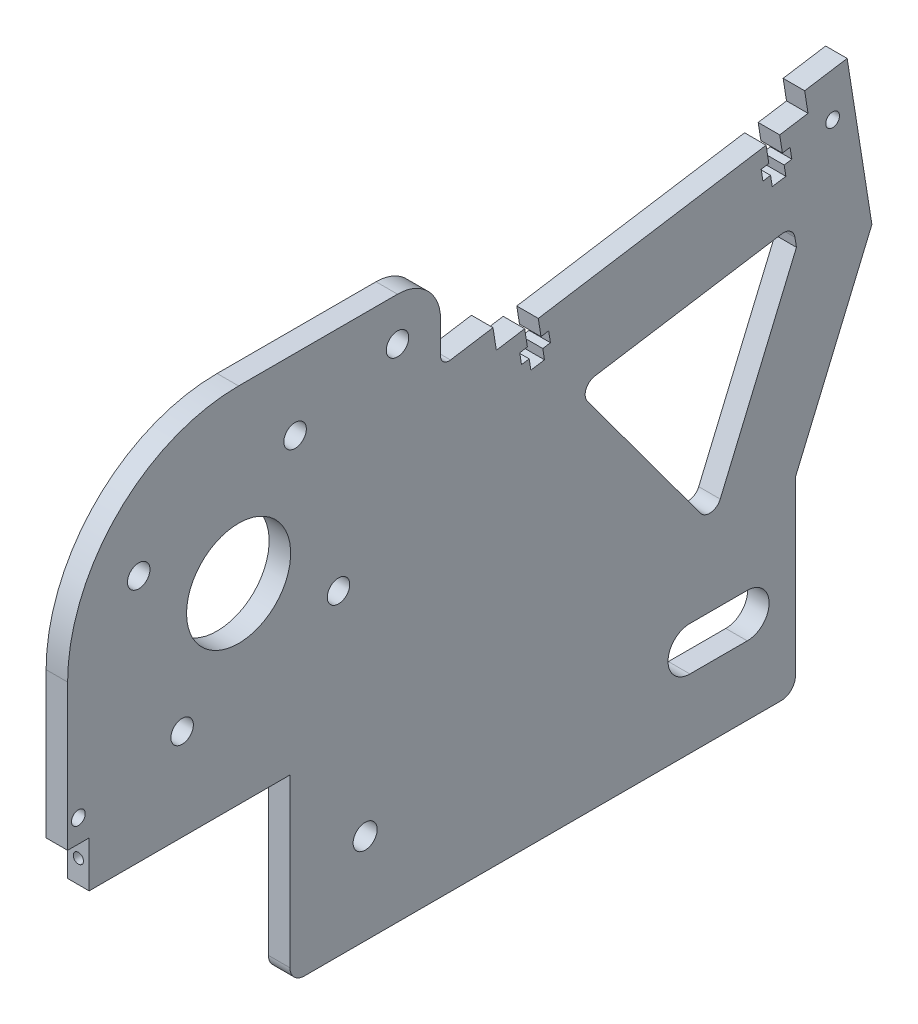
SolidWorks part; units mm, degrees
ref_plane "Front Plane" through (0, 0, 0) normal (0, 0, 1) x (1, 0, 0)
ref_plane "Top Plane" through (0, 0, 0) normal (0, 1, 0) x (1, 0, 0)
ref_plane "Right Plane" through (0, 0, 0) normal (1, 0, 0) x (0, 0, -1)
sketch "Sketch1" plane through (0, 0, 0) normal (1, 0, 0) x (0, 0, -1)
  line L0 (-28.1703, 0) -> (77.3828, 0)
  line L1 (80.5578, 3.175) -> (80.5578, 41.307)
  line L2 (-80.5578, 82.55) -> (-80.5578, 50.292)
  line L3 (4.1952, 101.9194) -> (13.6029, 103.4094)
  line L4 (-75.7953, 50.292) -> (-75.7953, 40.132)
  line L5 (-80.5578, 50.292) -> (-75.7953, 50.292)
  line L6 (69.8898, 20.066) -> (57.1898, 20.066) construction
  line L7 (-75.7953, 40.132) -> (-31.3453, 40.132)
  line L8 (1.9922, 110.875) -> (1.9922, 103.8009)
  line L9 (-42.7078, 120.4) -> (-7.5328, 120.4)
  line L10 (-31.3453, 40.132) -> (-31.3453, 3.175)
  line L11 (-37.9611, 96.6304) -> (82.0608, 56.1697) construction
  line L12 (-52.1443, 71.0721) -> (45.6937, -9.3646) construction
  line L13 (69.8898, 15.2273) -> (57.1898, 15.2273)
  line L14 (69.8898, 24.9047) -> (57.1898, 24.9047)
  line L15 (4.1952, 101.9194) -> (101.0919, 101.9194) construction
  line L16 (13.6029, 103.4094) -> (14.348, 98.7055)
  line L17 (14.348, 98.7055) -> (20.6198, 99.6989)
  line L18 (83.338, 109.6325) -> (82.593, 114.3363)
  line L19 (82.593, 114.3363) -> (92.0007, 115.8264)
  line L20 (92.0007, 115.8264) -> (97.4765, 81.2539)
  line L21 (97.4765, 81.2539) -> (80.5578, 41.307)
  line L22 (20.6198, 99.6989) -> (21.2208, 95.9044)
  line L23 (21.2208, 95.9044) -> (19.5274, 95.6362)
  line L24 (19.5274, 95.6362) -> (19.9198, 93.1589)
  line L25 (19.9198, 93.1589) -> (21.6131, 93.4271)
  line L26 (26.317, 94.1721) -> (25.9246, 96.6495)
  line L27 (25.9246, 96.6495) -> (24.2312, 96.3812)
  line L28 (24.2312, 96.3812) -> (23.6303, 100.1757)
  line L29 (23.6303, 100.1757) -> (74.0557, 108.1623)
  line L30 (77.0662, 108.6391) -> (83.338, 109.6325)
  line L31 (80.4436, 87.3149) -> (80.7745, 85.2255)
  line L38 (21.6131, 93.4271) -> (21.9857, 91.0751)
  line L39 (21.9857, 91.0751) -> (24.9961, 91.5519)
  line L40 (24.9961, 91.5519) -> (24.6236, 93.9039)
  line L41 (24.6236, 93.9039) -> (26.317, 94.1721)
  line L46 (74.0557, 108.1623) -> (74.6567, 104.3679)
  line L47 (77.5375, 89.4263) -> (36.1485, 82.8709)
  line L48 (34.5006, 78.856) -> (59.5216, 44.8808)
  line L49 (63.9057, 45.3965) -> (80.7745, 85.2255)
  line L50 (74.6567, 104.3679) -> (72.9633, 104.0996)
  line L51 (72.9633, 104.0996) -> (73.3557, 101.6223)
  line L52 (73.3557, 101.6223) -> (75.0491, 101.8905)
  line L53 (79.7529, 102.6355) -> (79.3605, 105.1129)
  line L54 (79.3605, 105.1129) -> (77.6672, 104.8447)
  line L55 (77.6672, 104.8447) -> (77.0662, 108.6391)
  line L56 (75.0491, 101.8905) -> (75.4216, 99.5385)
  line L57 (75.4216, 99.5385) -> (78.432, 100.0154)
  line L58 (78.432, 100.0154) -> (78.0595, 102.3673)
  line L59 (78.0595, 102.3673) -> (79.7529, 102.6355)
  arc A0 (69.8898, 15.2273) -> (69.8898, 24.9047) centre (69.8898, 20.066) ccw
  circle A1 centre (-42.7078, 82.55) radius 31.5 construction
  circle A2 centre (69.8898, 20.066) radius 78.105 construction
  circle A3 centre (69.8898, 20.066) radius 38.1 construction
  circle A4 centre (-42.7078, 82.55) radius 14.859 construction
  arc A5 (-42.7078, 120.4) -> (-80.5578, 82.55) centre (-42.7078, 82.55) ccw
  arc A6 (-28.1703, 0) -> (-31.3453, 3.175) centre (-28.1703, 3.175) cw
  arc A7 (77.3828, 0) -> (80.5578, 3.175) centre (77.3828, 3.175) ccw
  circle A9 centre (-7.5328, 110.875) radius 6.35 construction
  circle A10 centre (-55.209, 60.4394) radius 2.4892
  circle A11 centre (-14.6922, 20.066) radius 2.667
  circle A12 centre (-20.5972, 70.0488) radius 2.4892
  circle A13 centre (-64.8184, 95.0512) radius 2.4892
  circle A14 centre (-30.2065, 104.6606) radius 2.4892
  circle A15 centre (-78.1765, 55.372) radius 1.524
  circle A16 centre (-42.7078, 82.55) radius 11.5228
  arc A17 (57.1898, 24.9047) -> (57.1898, 15.2273) centre (57.1898, 20.066) ccw
  arc A18 (-7.5328, 120.4) -> (1.9922, 110.875) centre (-7.5328, 110.875) cw
  circle A19 centre (-7.5328, 110.875) radius 2.4892
  arc A20 (4.1952, 101.9194) -> (1.9922, 103.8009) centre (3.8972, 103.8009) cw
  circle A22 centre (88.7869, 105.6736) radius 1.524
  arc A24 (59.5216, 44.8808) -> (63.9057, 45.3965) centre (61.5669, 46.387) ccw
  arc A25 (36.1485, 82.8709) -> (34.5006, 78.856) centre (36.5458, 80.3622) ccw
  arc A26 (77.5375, 89.4263) -> (80.4436, 87.3149) centre (77.9349, 86.9176) cw
  point P39 (63.5398, 20.066)
  dimension "D4" = 9.6774
  dimension "D7" = 29.718
  dimension "D8" = 63
  dimension "D9" = 6.35
  dimension "D12" = 3.175
  dimension "D13" = 4.7625
  dimension "D14" = 76.2
  dimension "D15" = 156.21
  dimension "D18" = 5.334
  dimension "D19" = 9.525
  dimension "D20" = 9.525
  dimension "D23" = 3.048
  dimension "D27" = 73.025
  dimension "D28" = 12.7
  dimension "D29" = 4.9784
  dimension "D31" = 1.905
  dimension "D33" = 3.048
  dimension "D42" = 2.54
  dimension "D44" = 86.36
  dimension "D48" = 3.048
  dimension "D49" = 9.525
  dimension "D2" = 40.132
  dimension "D3" = 20.066
  dimension "D5" = 10.668
  dimension "D6" = 44.45
  dimension "D10" = 161.1156
  dimension "D11" = 95.25
  dimension "D17" = 9
  dimension "D21" = 4.7625
  dimension "D22" = 10.16
  dimension "D24" = 5.08
  dimension "D25" = 2.3813
  dimension "D26" = 12.7
  dimension "D16" = 88.9
  dimension "D30" = 9.525
  dimension "D34" = 19.05
  dimension "D35" = 8.7312
  dimension "D36" = 2.5083
  dimension "D37" = 6.477
  dimension "D38" = 6.35
  dimension "D40" = 15.875
  dimension "D45" = 6.35
  dimension "D46" = 6.35
  dimension "D47" = 4.7625
  dimension "D50" = 5.08
  dimension "D39" = 2
extrude "Boss-Extrude1" add sketch "Sketch1" along normal blind 4.7625
sketch "Sketch2" plane through (0, 0, 75.7953) normal (0, 0, 1) x (1, 0, 0)
  line L0 (4.7625, 50.292) -> (4.7625, 40.132) construction
  line L1 (4.7625, 40.132) -> (0, 40.132) construction
  circle A0 centre (2.3813, 45.212) radius 1.1303
  point P4 (4.7625, 45.212)
  point P7 (2.3813, 40.132)
  dimension "D1" = 2.2606
extrude "Cut-Extrude1" cut sketch "Sketch2" against normal blind 6.35
